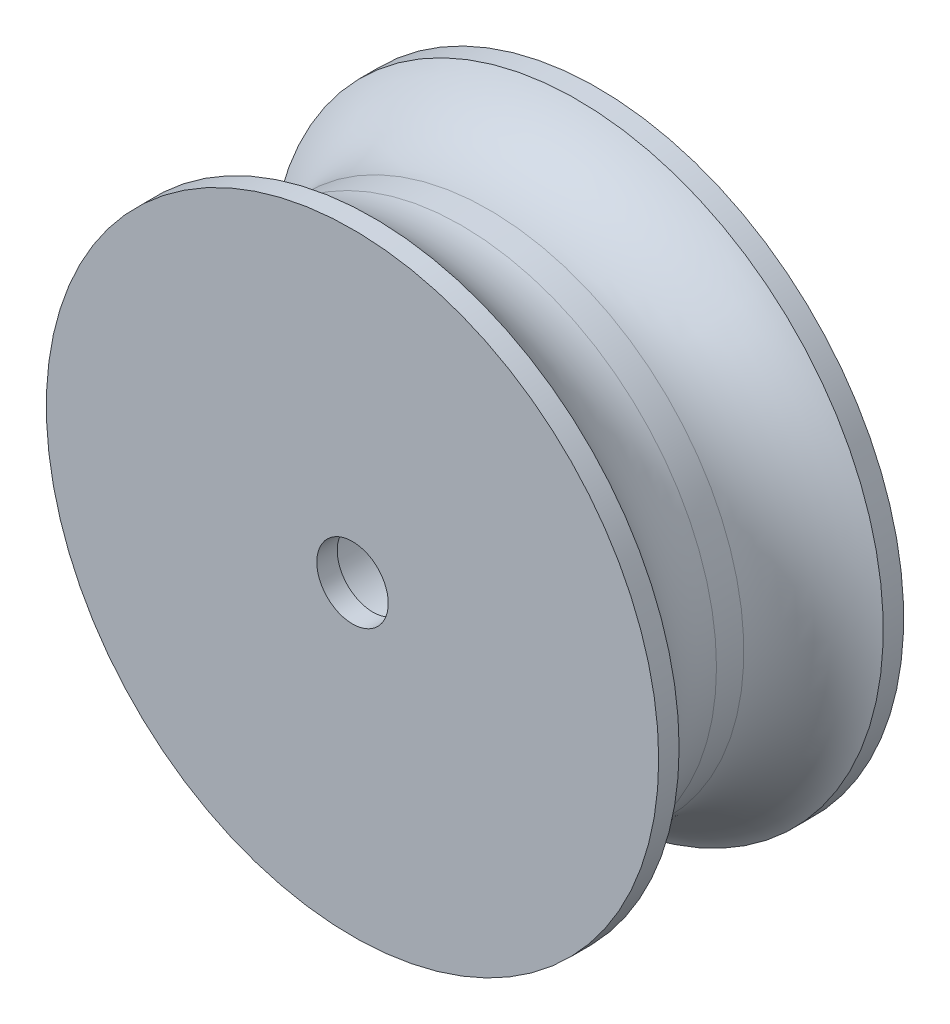
SolidWorks part; units mm, degrees
material "Polyethylene Cross-Linked"
ref_plane "Front Plane" through (0, 0, 0) normal (0, 0, 1) x (1, 0, 0)
ref_plane "Top Plane" through (0, 0, 0) normal (0, 1, 0) x (1, 0, 0)
ref_plane "Right Plane" through (0, 0, 0) normal (1, 0, 0) x (0, 0, -1)
sketch "Sketch1" plane through (0, 0, 0) normal (0, 0, 1) x (1, 0, 0)
  circle A0 centre (0, 0) radius 12.5
  dimension "D1" = 25
extrude "Boss-Extrude1" add sketch "Sketch1" along normal blind 10
sketch "Sketch4" plane through (0, 0, 10) normal (0, 0, 1) x (1, 0, 0)
  circle A0 centre (0, 0) radius 1.75
hole_wizard "#6 (0.204) Diameter Slot2" positions "Sketch6" profile "Sketch5" size "#6" standard "ANSI Inch" slot yes end condition through all
sketch "Sketch6" plane through (0, 0, 10) normal (0, 0, 1) x (1, 0, 0)
  point P0 (0, 0)
sketch "Sketch5" plane through (0, 0, 10) normal (1, 0, 0) x (0, -1, 0)
  line L0 (0, 0) -> (0, 10)
  line L1 (0, 10) -> (2.5908, 10)
  line L2 (2.5908, 10) -> (2.5908, 0)
  line L5 (2.5908, 0) -> (0, 0)
  line L11 (0, -6.35) -> (0, 107.95) construction
  dimension "Thru Hole Dia." = 5.1816
  dimension "Thru Hole Depth" = 10
sketch "Sketch10" plane through (0, 0, 0) normal (0, 0, -1) x (-1, 0, 0)
  circle A0 centre (0, 0) radius 15
extrude "Boss-Extrude2" add sketch "Sketch10" along normal blind 1
sketch "Sketch12" plane through (0, 0, 10) normal (0, 0, 1) x (1, 0, 0)
  circle A0 centre (0, 0) radius 15
extrude "Boss-Extrude3" add sketch "Sketch12" along normal blind 1
sketch "Sketch13" plane through (0, 0, 11) normal (0, 0, 1) x (1, 0, 0)
  circle A0 centre (0, 0) radius 1.75
extrude "Cut-Extrude1" cut sketch "Sketch13" against normal through all
fillet "Fillet4" radius 5 1 edges at (12.5, 0, 10)
fillet "Fillet5" radius 5 1 edges at (-12.5, 0, 0)
